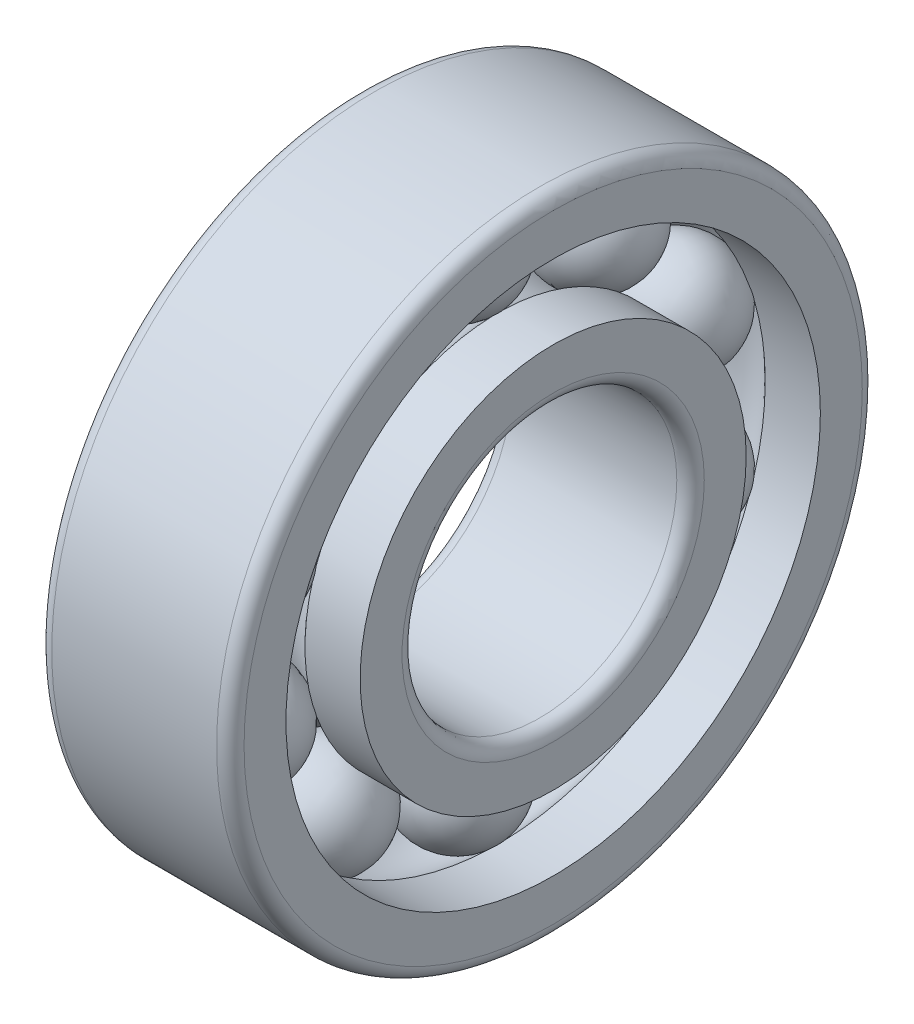
SolidWorks part; units mm, degrees
material "Alloy Steel"
ref_plane "Plane1" through (0, 0, 0) normal (0, 0, 1) x (1, 0, 0)
ref_plane "Plane2" through (0, 0, 0) normal (0, 1, 0) x (1, 0, 0)
ref_plane "Plane3" through (0, 0, 0) normal (1, 0, 0) x (0, 0, -1)
other "Configuration Table"
sketch "Clipboard" plane through (0, 0, 0) normal (0, 0, 1) x (1, 0, 0)
  line L0 (-10, 0) -> (10, 0) construction
  line L1 (0, 0) -> (22.021, -3.8829)
  line L2 (0, 0) -> (16.4955, 2.9086)
  line L3 (0, 0) -> (22.021, -3.8829)
  line L4 (0, 0) -> (-22.3573, -0.3902)
  dimension "BallCLRad" = 16.75
  dimension "Count" = 10
sketch "CagSpiSke" plane through (0, 0, 0) normal (0, 0, 1) x (1, 0, 0)
  line L0 (0.405, 16.075) -> (0.405, 17.425)
  line L1 (0.405, 17.425) -> (-0.405, 17.425)
  line L2 (-0.405, 17.425) -> (-0.405, 16.075)
  line L3 (-0.405, 16.075) -> (0.405, 16.075)
  line L4 (-20.6375, 0) -> (20.6375, 0) construction
  line L5 (0, 0) -> (0, 23.7692) construction
  dimension "OD" = 34.85
  dimension "ID" = 32.15
revolve "CageSpine" add sketch "CagSpiSke" angle 0.001 about L4 reverse direction yes
ref_axis "Axis1" through (-50, 0, 0) along (1, 0, 0)
sketch "CagBalSke" plane through (0, 0, 0) normal (0, 0, 1) x (1, 0, 0)
  line L0 (-4.455, 16.75) -> (4.455, 16.75)
  line L1 (-1.905, 16.75) -> (1.905, 16.75) construction
  line L2 (-10, 0) -> (10, 0) construction
  line L3 (0, 0) -> (0, 24) construction
  arc A0 (4.455, 16.75) -> (-4.455, 16.75) centre (0, 16.75) cw
  dimension "BallCLRad" = 16.75
revolve "CageBall" [suppressed] add sketch "CagBalSke" angle 360 about L1 reverse direction yes
pattern_circular "CageBalls" [suppressed] count 10 every 36 about axis through (-50, 0, 0) along (1, 0, 0)
sketch "CagTrmODSke" plane through (0, 0, 0) normal (0, 0, 1) x (1, 0, 0)
  line L0 (4.456, 17.425) -> (4.456, 21.206)
  line L1 (4.456, 21.206) -> (-4.456, 21.206)
  line L2 (-4.456, 21.206) -> (-4.456, 17.425)
  line L3 (-4.456, 17.425) -> (4.456, 17.425)
  line L4 (-20.6375, 0) -> (20.6375, 0) construction
  line L5 (0, 0) -> (0, 25) construction
  dimension "Width" = 8.912
  dimension "ID" = 34.85
  dimension "OD" = 42.412
revolve "CageTrimOD" [suppressed] cut sketch "CagTrmODSke" angle 360 about L4 reverse direction yes
sketch "CagTrmIDSke" plane through (0, 0, 0) normal (0, 0, 1) x (1, 0, 0)
  line L0 (4.456, 12.296) -> (4.456, 16.075)
  line L1 (4.456, 16.075) -> (-4.456, 16.075)
  line L2 (-4.456, 16.075) -> (-4.456, 12.296)
  line L3 (-4.456, 12.296) -> (4.456, 12.296)
  line L4 (-20.6375, 0) -> (20.6375, 0) construction
  line L5 (0, 0) -> (0, 25) construction
  dimension "Width" = 8.912
  dimension "ID" = 24.592
  dimension "OD" = 32.15
revolve "CageTrimID" [suppressed] cut sketch "CagTrmIDSke" angle 360 about L4 reverse direction yes
sketch "BalSimSke" plane through (0, 0, 0) normal (0, 0, 1) x (1, 0, 0)
  line L0 (-10, 0) -> (10, 0) construction
  line L1 (-10, 16.75) -> (10, 16.75) construction
  line L2 (0, 0) -> (0, 23) construction
  circle A0 centre (0, 16.75) radius 4.05
  dimension "BallCLRad" = 16.75
revolve "BallsSimplified" [suppressed] add sketch "BalSimSke" angle 360 about L0
sketch "BalDetSke" plane through (0, 0, 0) normal (0, 0, 1) x (1, 0, 0)
  line L0 (-4.05, 16.75) -> (4.05, 16.75)
  line L1 (-1.905, 16.75) -> (1.905, 16.75) construction
  line L2 (0, 0) -> (0, 25) construction
  arc A0 (4.05, 16.75) -> (-4.05, 16.75) centre (0, 16.75) cw
  dimension "BallCLRad" = 16.75
revolve "BallDetailed" add sketch "BalDetSke" angle 360 about L1 reverse direction yes
sketch "InnRacSke" plane through (0, 0, 0) normal (0, 0, 1) x (1, 0, 0)
  line L0 (-2.9851, 14.05) -> (-7, 14.05)
  line L1 (-7, 14.05) -> (-7, 11)
  line L2 (-6, 10) -> (6, 10)
  line L3 (7, 11) -> (7, 14.05)
  line L4 (7, 14.05) -> (2.9851, 14.05)
  line L5 (-20.6375, 0) -> (20.6375, 0) construction
  line L6 (0, 0) -> (0, 30) construction
  arc A0 (-7, 11) -> (-6, 10) centre (-6, 11) ccw
  arc A1 (6, 10) -> (7, 11) centre (6, 11) ccw
  arc A2 (2.9851, 14.05) -> (-2.9851, 14.05) centre (0, 16.75) cw
  dimension "BallCLRad" = 16.75
  dimension "Fillet_radius" = 1
  dimension "Ball_diameter" = 8.05
  dimension "ID" = 20
  dimension "OD" = 28.1
  dimension "Width" = 14
revolve "InnerRace" add sketch "InnRacSke" angle 360 about L5 reverse direction yes
sketch "OutRacSke" plane through (0, 0, 0) normal (0, 0, 1) x (1, 0, 0)
  line L0 (-2.9851, 19.45) -> (-7, 19.45)
  line L1 (-7, 19.45) -> (-7, 22.5)
  line L2 (-6, 23.5) -> (6, 23.5)
  line L3 (7, 22.5) -> (7, 19.45)
  line L4 (7, 19.45) -> (2.9851, 19.45)
  line L5 (-20.6375, 0) -> (20.6375, 0) construction
  line L6 (0, 0) -> (0, 30) construction
  arc A0 (-7, 22.5) -> (-6, 23.5) centre (-6, 22.5) cw
  arc A1 (6, 23.5) -> (7, 22.5) centre (6, 22.5) cw
  arc A2 (2.9851, 19.45) -> (-2.9851, 19.45) centre (0, 16.75) ccw
  dimension "BallCLRad" = 16.75
  dimension "Fillet_radius" = 1
  dimension "Ball_diameter" = 8.05
  dimension "Width" = 14
revolve "OuterRace" add sketch "OutRacSke" angle 360 about L5 reverse direction yes
pattern_circular "BallsDetailed" count 10 every 36 about axis through (-50, 0, 0) along (1, 0, 0) of "BallDetailed"
equation "\"BallCLRad@Clipboard\" = ( \"OD@OutRacSke\" + \"ID@InnRacSke\" ) / 4"
equation "\"BallCLRad@BalSimSke\" = \"BallCLRad@Clipboard\""
equation "\"BallCLRad@BalDetSke\" = \"BallCLRad@Clipboard\""
equation "\"BallCLRad@InnRacSke\" = \"BallCLRad@Clipboard\""
equation "\"BallCLRad@OutRacSke\" = \"BallCLRad@Clipboard\""
equation "\"Ball_diameter@InnRacSke\" = \"Ball_diameter@BalDetSke\" - 0.05"
equation "\"Ball_diameter@OutRacSke\" = \"Ball_diameter@BalDetSke\" - 0.05"
equation "\"Ball_diameter@BalSimSke\" = \"Ball_diameter@BalDetSke\""
equation "\"Width@OutRacSke\" = \"Width@InnRacSke\""
equation "\"Fillet_radius@OutRacSke\" = \"Fillet_radius@InnRacSke\""
equation "\"Max_count@Clipboard\" = int( 3.14159265 / atn(( \"Ball_diameter@BalDetSke\" / 2) / sqr( \"BallCLRad@Clipboard\"  *  \"BallCLRad@Clipboard\" - ( \"Ball_diameter@BalDetSke\" / 2) *  ( \"Ball_diameter@BalDetSke\" / 2))))"
equation "\"Max_count@Clipboard\" = ((sgn( \"Max_count@Clipboard\" - \"Count@Clipboard\" )-1)*( \"Max_count@Clipboard\" - \"Count@Clipboard\" ))/-2+ \"Count@Clipboard\""
equation "\"Count@BallsDetailed\" = int( \"Show_count@Clipboard\" ) "
equation "\"Count@BallsDetailed\" = ((sgn( \"Count@BallsDetailed\" - \"Max_count@Clipboard\" )-1)*( \"Count@BallsDetailed\" - \"Max_count@Clipboard\" ))/-2+ \"Max_count@Clipboard\""
equation "\"Count@BallsDetailed\" = ((sgn( \"Count@BallsDetailed\" - \"Min_count@Clipboard\" )+1)*( \"Count@BallsDetailed\" - \"Min_count@Clipboard\"))/2 +\"Min_count@Clipboard\""
equation "\"Angle@BallsDetailed\" = 360.0 / \"Max_count@Clipboard\""
equation "\"BallCLRad@CagBalSke\" = \"BallCLRad@Clipboard\""
equation "\"Count@CageBalls\" = \"Count@BallsDetailed\""
equation "\"Angle@CageBalls\" = \"Angle@BallsDetailed\""
equation "\"Angle@CageSpine\" =  \"Angle@CageBalls\" * ( \"Count@CageBalls\" -1 + int( \"Count@CageBalls\" / \"Max_count@Clipboard\" ) )  + 0.001 -  int( \"Count@CageBalls\" / \"Max_count@Clipboard\" ) * 0.001"
equation "\"Angle@CageSpine\" =  \"Angle@CageSpine\" * int( \"Min_count@Clipboard\" / 2) + int(1 / \"Min_count@Clipboard\")  * 0.001"
equation "\"CageWallOD@CagBalSke\" =  \"Ball_diameter@BalDetSke\" * 1.1"
equation "\"Thickness@CagSpiSke\" =  \"Ball_diameter@BalDetSke\" * 0.1"
equation "\"OD@CagTrmODSke\" = \"BallCLRad@Clipboard\" * 2 + \"CageWallOD@CagBalSke\" + 0.002"
equation "\"ID@CagTrmODSke\" = \"BallCLRad@Clipboard\" * 2 + \"Ball_diameter@BalDetSke\" / 6"
equation "\"OD@CagTrmIDSke\" = \"BallCLRad@Clipboard\" * 2 - \"Ball_diameter@BalDetSke\" / 6"
equation "\"ID@CagTrmIDSke\" = \"BallCLRad@Clipboard\" * 2 - \"CageWallOD@CagBalSke\" + 0.002"
equation "\"OD@CagSpiSke\" = \"ID@CagTrmODSke\""
equation "\"ID@CagSpiSke\" = \"OD@CagTrmIDSke\""
equation "\"Width@CagTrmODSke\" = \"CageWallOD@CagBalSke\" + 0.002"
equation "\"Width@CagTrmIDSke\" = \"CageWallOD@CagBalSke\" + 0.002"
